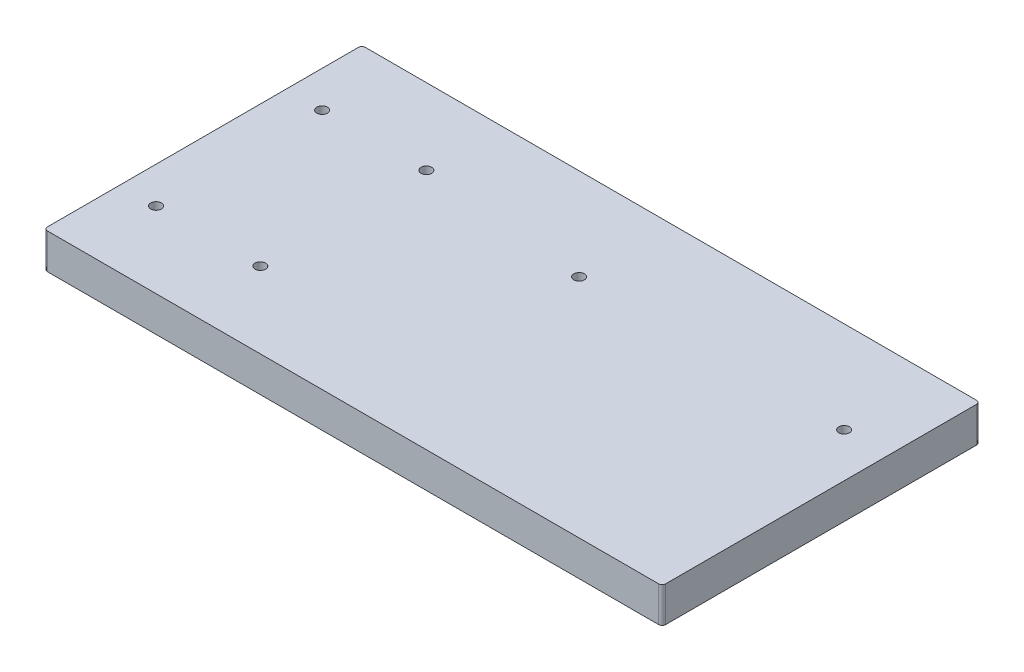
SolidWorks part; units mm, degrees
ref_plane "Front Plane" through (0, 0, 0) normal (0, 0, 1) x (1, 0, 0)
ref_plane "Top Plane" through (0, 0, 0) normal (0, 1, 0) x (1, 0, 0)
ref_plane "Right Plane" through (0, 0, 0) normal (1, 0, 0) x (0, 0, -1)
sketch "Sketch1" plane through (0, 0, 0) normal (0, 1, 0) x (1, 0, 0)
  line L1 (87.5, -45) -> (-87.5, -45)
  line L2 (87.5, -45) -> (87.5, 45)
  line L3 (87.5, 45) -> (-87.5, 45)
  line L4 (-87.5, -45) -> (-87.5, 45)
  line L5 (87.5, -45) -> (-87.5, 45) construction
  line L6 (87.5, 45) -> (-87.5, -45) construction
  point P0 (0, 0)
  dimension "D1" = 175
  dimension "D2" = 90
extrude "Boss-Extrude1" add sketch "Sketch1" along normal blind 10
sketch "Sketch2" plane through (0, 10, 0) normal (0, 1, 0) x (1, 0, 0)
  line L0 (-87.5, 45) -> (-87.5, -45) construction
  line L5 (-62.5, -23.5) -> (-62.5, 0) construction
  line L7 (0, 0) -> (-87.5, 0) construction
  line L12 (-77.25, -23.5) -> (-47.75, -23.5) construction
  circle A0 centre (0, 19) radius 1.5
  circle A1 centre (75, 19) radius 1.5
  circle A2 centre (-77.25, -23.5) radius 1.5
  circle A3 centre (-47.75, -23.5) radius 1.5
  point P0 (-62.5, -23.5)
  point P3 (-62.5, -23.5)
  point P14 (-62.5, -17.692)
  point P17 (0, 0)
  point P18 (0, 0)
  dimension "D6" = 19
  dimension "D8" = 3
  dimension "D2" = 3
  dimension "D1" = 29.5
  dimension "D3" = 23.5
  dimension "D4" = 25
  dimension "D5" = 62.5
  dimension "D7" = 75
extrude "Cut-Extrude1" cut sketch "Sketch2" against normal through all contours A2 | A3 region at (-77.25, 10, 23.5) region at (-47.75, 10, 23.5)
mirror "Mirror1" about plane through (0, 0, 0) normal (0, 0, 1) of "Cut-Extrude1"
fillet "Fillet1" radius 1 4 edges at (-87.5, 5, -45) (87.5, 5, -45) (87.5, 5, 45) (-87.5, 5, 45)
extrude "Cut-Extrude2" cut sketch "Sketch2<9>" against normal through all contours A1 | A0 region at (0, 10, -19) region at (75, 10, -19)
sketch "Sketch2<9>" plane through (0, 10, 0) normal (0, 1, 0) x (1, 0, 0) same geometry as "Sketch2"
